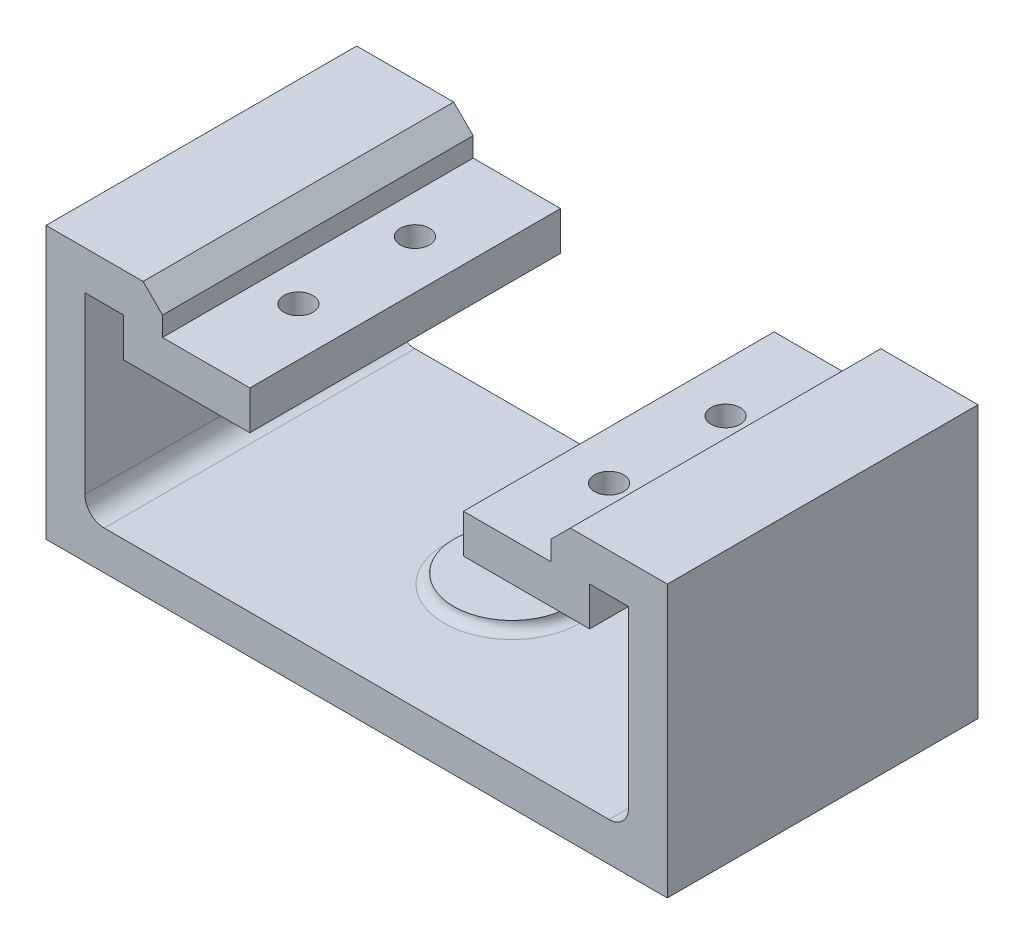
SolidWorks part; units mm, degrees
material "AISI 4340 Steel, annealed"
ref_plane "Front Plane" through (0, 0, 0) normal (0, 0, 1) x (1, 0, 0)
ref_plane "Top Plane" through (0, 0, 0) normal (0, 1, 0) x (1, 0, 0)
ref_plane "Right Plane" through (0, 0, 0) normal (1, 0, 0) x (0, 0, -1)
sketch "Sketch1" plane through (0, 0, 0) normal (0, 0, 1) x (1, 0, 0)
  line L0 (0, 39.3952) -> (0, -23.9317) construction
  line L1 (0, -55) -> (0, 55) construction
  line L2 (34.925, 76.2) -> (63.5, 76.2)
  line L3 (-34.925, 76.2) -> (-63.5, 76.2)
  line L4 (63.5, 76.2) -> (63.5, 88.9)
  line L5 (-63.5, 76.2) -> (-63.5, 88.9)
  line L6 (63.5, 88.9) -> (101.6, 88.9)
  line L7 (-63.5, 88.9) -> (-101.6, 88.9)
  line L8 (101.6, 88.9) -> (101.6, 0)
  line L9 (55, 0) -> (-55, 0) construction
  line L10 (-101.6, 88.9) -> (-101.6, 0)
  line L11 (101.6, 0) -> (-101.6, 0)
  line L12 (34.925, 76.2) -> (34.925, 63.5)
  line L13 (-34.925, 76.2) -> (-34.925, 63.5)
  line L14 (34.925, 63.5) -> (76.2, 63.5)
  line L15 (-34.925, 63.5) -> (-76.2, 63.5)
  line L16 (76.2, 63.5) -> (76.2, 76.2)
  line L17 (-76.2, 63.5) -> (-76.2, 76.2)
  line L18 (76.2, 76.2) -> (88.9, 76.2)
  line L19 (-76.2, 76.2) -> (-88.9, 76.2)
  line L20 (88.9, 76.2) -> (88.9, 12.7)
  line L21 (-88.9, 76.2) -> (-88.9, 12.7)
  line L22 (88.9, 12.7) -> (-88.9, 12.7)
  point P17 (0, 0)
  point P28 (0, 12.7)
  dimension "D1" = 203.2
  dimension "D2" = 177.8
  dimension "D3" = 12.7
  dimension "D4" = 76.2
  dimension "D5" = 88.9
  dimension "D6" = 12.7
  dimension "D7" = 69.85
  dimension "D8" = 127
  dimension "D9" = 63.5
  dimension "D10" = 152.4
extrude "Boss-Extrude1" add sketch "Sketch1" along normal mid plane 101.6
sketch "Sketch2" plane through (0, 76.2, 0) normal (0, 1, 0) x (1, 0, 0)
  line L0 (0, -48.895) -> (0, 48.895) construction
  line L1 (-48.895, 0) -> (48.895, 0) construction
  circle A0 centre (-50.8, 19.05) radius 4.7625
  circle A1 centre (-50.8, -19.05) radius 4.7625
  circle A2 centre (50.8, 19.05) radius 4.7625
  circle A3 centre (50.8, -19.05) radius 4.7625
  point P12 (0, 0)
  point P13 (0, 0)
  point P14 (0, 0)
  point P15 (0, 0)
  point P16 (0, 0)
  dimension "D1" = 9.525
  dimension "D2" = 50.8
  dimension "D3" = 19.05
  dimension "D4" = 19.05
  dimension "D5" = 50.8
extrude "Cut-Extrude1" cut sketch "Sketch2" against normal up to next
sketch "Sketch3" plane through (0, 12.7, 0) normal (0, 1, 0) x (1, 0, 0)
  circle A0 centre (0, 0) radius 19.05
  dimension "D1" = 38.1
extrude "Boss-Extrude2" add sketch "Sketch3" along normal mid plane 6.35
fillet "Fillet1" radius 6.35 2 edges at (88.9, 12.7, 0) (-88.9, 12.7, 0)
fillet "Fillet2" radius 3.175 1 edges at (19.05, 12.7, 0)
chamfer "Chamfer1" distance 6.35 angle 45 2 edges at (63.5, 88.9, 0) (-63.5, 88.9, 0)
